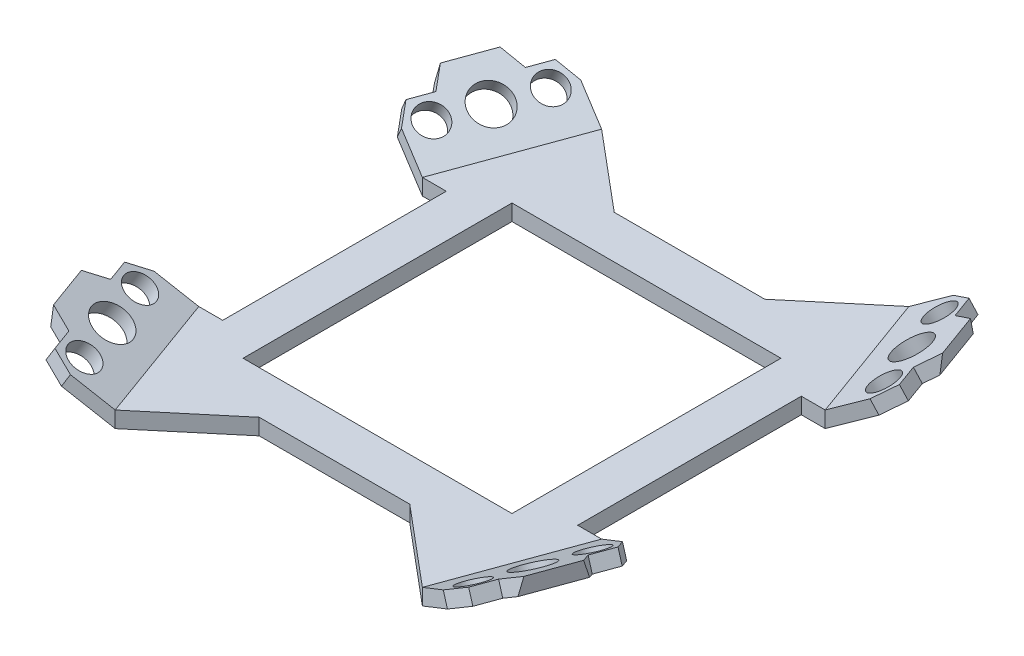
SolidWorks part; units mm, degrees
ref_plane "Front Plane" through (0, 0, 0) normal (0, 0, 1) x (1, 0, 0)
ref_plane "Top Plane" through (0, 0, 0) normal (0, 1, 0) x (1, 0, 0)
ref_plane "Right Plane" through (0, 0, 0) normal (1, 0, 0) x (0, 0, -1)
sketch "Sketch11" plane through (0, 0, 0) normal (0, 1, 0) x (1, 0, 0)
  line L0 (-50, -50) -> (-50, 50)
  line L1 (-27.9905, -66) -> (27.9905, -66)
  line L2 (-66, -41.568) -> (-66, 17.136)
  line L3 (-27.9905, 66) -> (27.9905, 66)
  line L4 (66, -41.568) -> (66, 41.568)
  line L5 (-66, -66) -> (66, 66) construction
  line L6 (-66, 66) -> (66, -66) construction
  line L7 (-50, 50) -> (50, 50)
  line L8 (50, -50) -> (50, 50)
  line L9 (-50, -50) -> (50, -50)
  line L18 (-66, 17.136) -> (-66, 66) construction
  line L19 (-66, -66) -> (-66, 66) construction
  line L20 (66, 41.568) -> (66, 66) construction
  line L21 (66, -66) -> (66, 66) construction
  line L22 (66, -66) -> (66, -41.568) construction
  line L23 (-66, -66) -> (-66, -41.568) construction
  line L24 (-57.1075, 90.432) -> (-74.8925, 41.568)
  line L25 (-74.8925, 41.568) -> (-66, 41.568)
  line L26 (-66, 41.568) -> (-66, 17.136)
  line L27 (-57.1075, 90.432) -> (-27.9905, 66)
  line L28 (-66, 66) -> (-27.9905, 66) construction
  line L29 (-66, 66) -> (66, 66) construction
  line L30 (0, -55) -> (0, 55) construction
  line L31 (57.1075, 90.432) -> (27.9905, 66)
  line L32 (74.8925, 41.568) -> (66, 41.568)
  line L33 (57.1075, 90.432) -> (74.8925, 41.568)
  line L34 (-55, 0) -> (55, 0) construction
  line L35 (74.8925, -41.568) -> (66, -41.568)
  line L36 (57.1075, -90.432) -> (74.8925, -41.568)
  line L37 (57.1075, -90.432) -> (27.9905, -66)
  line L38 (-57.1075, -90.432) -> (-27.9905, -66)
  line L39 (-74.8925, -41.568) -> (-66, -41.568)
  line L40 (-57.1075, -90.432) -> (-74.8925, -41.568)
  line L41 (27.9905, 66) -> (66, 66) construction
  line L42 (27.9905, -66) -> (66, -66) construction
  line L43 (-66, -66) -> (66, -66) construction
  line L44 (-66, -66) -> (-27.9905, -66) construction
  point P0 (0, 0)
  point P14 (66, 40.5746)
  point P16 (66, -40.6533)
  point P19 (-66, 66)
  point P20 (0, 0)
  point P36 (-66, -40.6533)
  dimension "D1" = 132
  dimension "D2" = 132
  dimension "D4" = 52
  dimension "D8" = 20
  dimension "D12" = 70
  dimension "D3" = 16
extrude "Boss-Extrude6" add sketch "Sketch11" along normal blind 6
ref_plane "Plane1" through (4.5989, 0, -12.6355) normal (0.342, 0, -0.9397) x (0, -1, 0)
sketch "Sketch12" plane through (4.5989, 0, -12.6355) normal (0.342, 0, -0.9397) x (0, -1, 0)
  line L0 (-6, 84.593) -> (-21, 110.5738)
  line L1 (-21, 110.5738) -> (-15, 110.5738)
  line L2 (-15, 110.5738) -> (0, 84.593)
  line L4 (-6, 84.593) -> (0, 84.593)
  line L5 (-6, 84.593) -> (0, 84.593) construction
  point P8 (0, 0)
  point P9 (-6, 84.593)
  point P11 (0, 0)
  point P12 (0, 84.593)
  dimension "D1" = 6
  dimension "D2" = 30
  dimension "D3" = 60
extrude "Boss-Extrude7" add sketch "Sketch12" along normal blind 52
sketch "Sketch13" plane through (-17.4315, -32.1299, -6.3445) normal (0.4698, 0.866, 0.171) x (0.8827, -0.4609, -0.091)
  line L0 (-58.7744, 95.6929) -> (-78.9217, 47.7546) construction
  line L1 (-72.6027, 101.5047) -> (-44.946, 89.8812) construction
  line L2 (-92.7501, 53.5664) -> (-65.0934, 41.9429) construction
  line L3 (-72.6027, 101.5047) -> (-92.7501, 53.5664) construction
  line L5 (-79.321, 85.5193) -> (-92.7501, 53.5664) construction
  line L6 (-86.0318, 69.5517) -> (-80.8073, 62.6697)
  line L15 (-80.8073, 62.6697) -> (-84.1701, 54.6681)
  line L16 (-84.1701, 54.6681) -> (-78.9217, 47.7546)
  line L17 (-58.7744, 95.6929) -> (-67.3853, 94.6045)
  line L24 (-79.321, 85.5193) -> (-70.7482, 86.603)
  line L25 (-70.7482, 86.603) -> (-67.3853, 94.6045)
  line L37 (-78.9217, 47.7546) -> (-92.7501, 53.5664)
  line L38 (-92.7501, 53.5664) -> (-86.0318, 69.5517)
  line L39 (-79.321, 85.5193) -> (-72.6027, 101.5047)
  line L40 (-72.6027, 101.5047) -> (-58.7744, 95.6929)
  line L41 (-92.7501, 53.5664) -> (-86.0318, 69.5517) construction
  line L49 (-51.6643, 73.8959) -> (-56.9008, 80.7936) [skipped]
  line L51 (-67.5941, 87.0016) -> (-79.321, 85.5193) [skipped]
  line L52 (-89.3987, 61.5841) -> (-93.7045, 61.0399) construction
  line L53 (-61.7109, 49.9476) -> (-64.3351, 53.4043) construction
  line L54 (-70.3103, 48.8431) -> (-68.6287, 52.8441) [skipped]
  line L55 (-78.9217, 47.7546) -> (-70.3103, 48.8431) [skipped]
  line L56 (-75.5589, 55.7562) -> (-70.102, 56.4459) construction
  line L57 (-58.3751, 57.9282) -> (-51.6643, 73.8959) [skipped]
  circle A0 centre (-75.5587, 55.7566) radius 5.5
  circle A1 centre (-68.848, 71.7238) radius 7
  circle A2 centre (-62.1374, 87.6909) radius 5.5
  point P13 (-89.3947, 61.5502)
  point P16 (0, 0)
  point P19 (0, 0)
  point P21 (0, 0)
  dimension "D1" = 11
  dimension "D2" = 11
  dimension "D3" = 14
  dimension "D6" = 17.3397
  dimension "D4" = 17.32
  dimension "D5" = 17.32
  dimension "D7" = 17.3397
  dimension "D8" = 120
  dimension "D9" = 30
  dimension "D10" = 7.4833
  dimension "D11" = 30
extrude "Cut-Extrude1" cut sketch "Sketch13" against normal through all
mirror "Mirror3" about plane through (0, 0, 0) normal (1, 0, 0) of "Cut-Extrude1", "Boss-Extrude7"
mirror "Mirror4" about plane through (0, 0, 0) normal (0, 0, 1) of "Boss-Extrude7", "Cut-Extrude1", "Mirror3"
